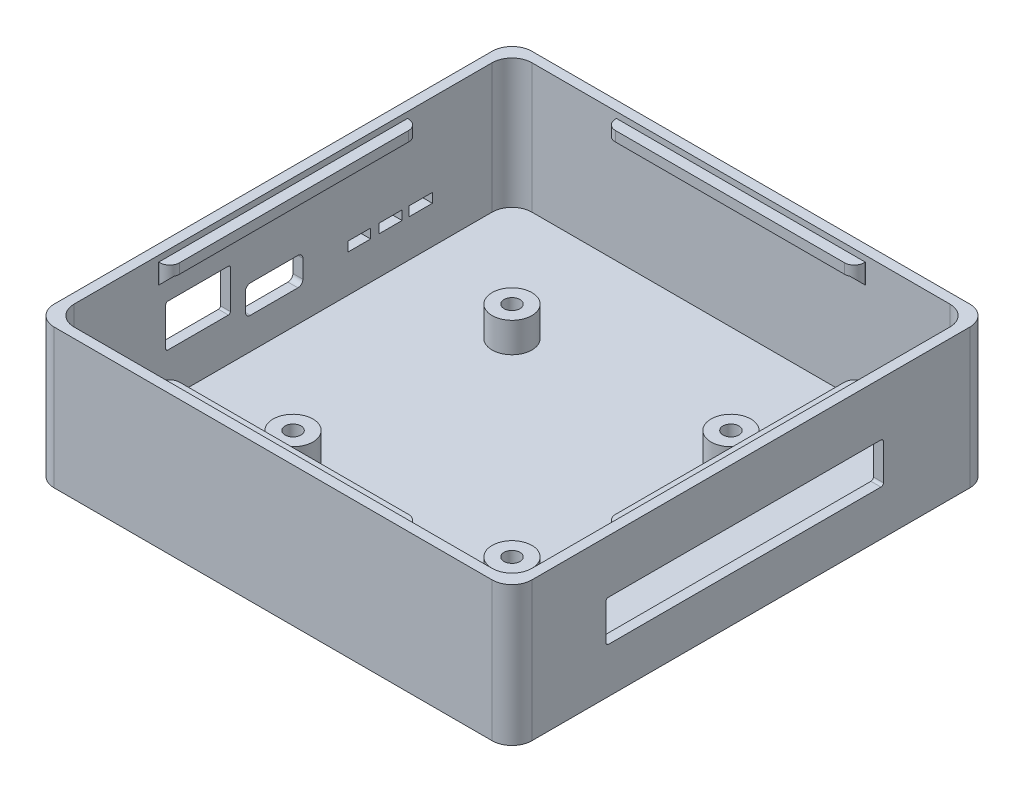
SolidWorks part; units mm, degrees
ref_plane "前视基准面" through (0, 0, 0) normal (0, 0, 1) x (1, 0, 0)
ref_plane "上视基准面" through (0, 0, 0) normal (0, 1, 0) x (1, 0, 0)
ref_plane "右视基准面" through (0, 0, 0) normal (1, 0, 0) x (0, 0, -1)
other "Configuration Table"
sketch "草图1" plane through (0, 0, 0) normal (0, 1, 0) x (1, 0, 0)
  line L1 (0, 0) -> (96, 0)
  line L2 (0, 0) -> (0, -96)
  line L3 (0, -96) -> (96, -96)
  line L4 (96, 0) -> (96, -96)
  dimension "D1" = 96
extrude "凸台-拉伸1" add sketch "草图1" along normal blind 28
sketch "草图3" plane through (0, 28, 0) normal (0, 1, 0) x (1, 0, 0)
  line L0 (96, 0) -> (0, 0) construction
  line L1 (2, -2) -> (94, -2)
  line L2 (2, -2) -> (2, -94)
  line L3 (2, -94) -> (94, -94)
  line L4 (94, -2) -> (94, -94)
  line L5 (0, 0) -> (0, -96) construction
  line L6 (96, -96) -> (96, 0) construction
  dimension "D1" = 92
  dimension "D2" = 2
  dimension "D3" = 2
extrude "切除-拉伸1" cut sketch "草图3" against normal offset from surface (26 mm away) 2 up to face at (48, 0, 48)
fillet "圆角1" radius 4 4 edges at (2, 15, 2) (94, 15, 2) (94, 15, 94) (2, 15, 94)
fillet "圆角2" radius 4 4 edges at (96, 14, 96) (0, 14, 96) (0, 14, 0) (96, 14, 0)
sketch "草图4" plane through (0, 2, 0) normal (0, 1, 0) x (1, 0, 0)
  line L0 (6, -2) -> (90, -2) construction
  line L1 (4, -4) -> (92, -4) construction
  line L2 (4, -4) -> (4, -92) construction
  line L3 (4, -92) -> (92, -92) construction
  line L4 (92, -4) -> (92, -92) construction
  line L5 (2, -90) -> (2, -6) construction
  line L6 (48, -4) -> (48, -102.0052) construction
  line L7 (4, -48) -> (92, -48) construction
  line L8 (26, 4.0084) -> (26, -97.7392) construction
  line L9 (70, 4.0084) -> (70, -100.3714) construction
  line L10 (-6.2321, -26) -> (113.0331, -26) construction
  line L11 (-8.2289, -70) -> (112.307, -70) construction
  circle A0 centre (26, -26) radius 4
  circle A1 centre (70, -26) radius 4
  circle A2 centre (70, -70) radius 4
  circle A3 centre (26, -70) radius 4
  dimension "D8" = 8
  dimension "D9" = 22
  dimension "D1" = 88
  dimension "D2" = 2
  dimension "D3" = 2
  dimension "D4" = 22
  dimension "D5" = 22
  dimension "D6" = 22
  dimension "D7" = 22
extrude "凸台-拉伸2" add sketch "草图4" along normal blind 6
sketch "草图5" plane through (0, 8, 0) normal (0, 1, 0) x (1, 0, 0)
  circle A0 centre (26, -26) radius 1.6
  circle A3 centre (70, -26) radius 1.6
  circle A4 centre (26, -70) radius 1.6
  circle A5 centre (70, -70) radius 1.6
  dimension "D1" = 3.2
extrude "切除-拉伸2" cut sketch "草图5" along direction (0, 1, 0) on the side against the normal up to next (8 mm away)
sketch "草图6" plane through (0, 0, 0) normal (-1, 0, 0) x (0, 0, 1)
  line L0 (72.5871, 9.5862) -> (72.5871, 20.0862) construction
  line L1 (58.5871, 19.0862) -> (71.5871, 19.0862)
  line L2 (58.5871, 19.0862) -> (58.5871, 10.5862)
  line L3 (58.5871, 10.5862) -> (71.5871, 10.5862)
  line L4 (71.5871, 19.0862) -> (71.5871, 10.5862)
  line L5 (17.9947, 11.4358) -> (22.6947, 11.4358)
  line L6 (17.9947, 11.4358) -> (17.9947, 9.5358)
  line L7 (17.9947, 9.5358) -> (22.6947, 9.5358)
  line L8 (22.6947, 11.4358) -> (22.6947, 9.5358)
  line L9 (24.0907, 11.4358) -> (28.6907, 11.4358)
  line L10 (24.0907, 11.4358) -> (24.0907, 9.5862)
  line L11 (24.0907, 9.5862) -> (28.6907, 9.5862)
  line L12 (28.6907, 11.4358) -> (28.6907, 9.5862)
  line L13 (30.4137, 11.4358) -> (34.9137, 11.4358)
  line L14 (30.4137, 11.4358) -> (30.4137, 9.5358)
  line L15 (30.4137, 9.5358) -> (34.9137, 9.5358)
  line L16 (34.9137, 11.4358) -> (34.9137, 9.5358)
  line L17 (57.5871, 20.0862) -> (57.5871, 9.5862) construction
  line L18 (72.5871, 20.0862) -> (57.5871, 20.0862) construction
  line L20 (57.5871, 9.5862) -> (72.5871, 9.5862) construction
  line L21 (22.6947, 9.5358) -> (22.6947, 10.3814) construction
  line L22 (17.9947, 9.5358) -> (17.9947, 10.3814) construction
  line L23 (22.4947, 11.4358) -> (18.1947, 11.4358) construction
  line L24 (18.1947, 9.5358) -> (22.4947, 9.5358) construction
  line L26 (28.6907, 10.3814) -> (28.6907, 9.5358) construction
  line L27 (24.0907, 9.5358) -> (24.0907, 10.3814) construction
  line L28 (28.5907, 11.4358) -> (24.2907, 11.4358) construction
  line L29 (28.5208, 9.5862) -> (24.3399, 9.5862) construction
  line L30 (30.4137, 9.5358) -> (30.4137, 10.3814) construction
  line L31 (34.8137, 11.4358) -> (30.5137, 11.4358) construction
  line L32 (30.5137, 9.5358) -> (34.8137, 9.5358) construction
  line L33 (34.9137, 10.3814) -> (34.9137, 9.5358) construction
  line L34 (45.2273, 11.7569) -> (45.2273, 8.9953) construction
  line L35 (44.0273, 13.9797) -> (55.5713, 13.9797)
  line L36 (44.0273, 13.9797) -> (44.0273, 8.3374)
  line L37 (44.0273, 8.3374) -> (55.5713, 8.3374)
  line L38 (55.5713, 13.9797) -> (55.5713, 8.3374)
  line L39 (54.3713, 8.9953) -> (54.3713, 11.7569) construction
  line L40 (46.2501, 12.7797) -> (53.3485, 12.7797) construction
  line L41 (46.2501, 9.5374) -> (53.3485, 9.5374) construction
  point P27 (22.6947, 9.9586)
  point P38 (28.6907, 9.9586)
  dimension "D1" = 1
  dimension "D2" = 1
  dimension "D3" = 1
  dimension "D4" = 1
  dimension "D5" = 0
  dimension "D6" = 0
  dimension "D7" = 0
  dimension "D8" = 0
  dimension "D9" = 0
  dimension "D10" = 0
  dimension "D11" = 0
  dimension "D12" = 0
  dimension "D13" = 0
  dimension "D14" = 0
  dimension "D15" = 0
  dimension "D16" = 0
  dimension "D17" = 1.2
  dimension "D18" = 1.2
  dimension "D19" = 1.2
  dimension "D20" = 1.2
extrude "切除-拉伸3" cut sketch "草图6" along direction (-1, 0, 0) on the side against the normal up to next (2 mm away)
fillet "圆角3" radius 0.4 4 edges at (1, 10.5862, 71.5871) (1, 10.5862, 58.5871) (1, 19.0862, 58.5871) (1, 19.0862, 71.5871)
sketch "草图7" plane through (96, 0, 0) normal (1, 0, 0) x (0, 0, -1)
  line L0 (-75.1321, 13.6862) -> (-75.1321, 9.5862) construction
  line L1 (-77.1321, 17.2862) -> (-21.364, 17.2862)
  line L2 (-77.1321, 17.2862) -> (-77.1321, 9.0862)
  line L3 (-77.1321, 9.0862) -> (-21.364, 9.0862)
  line L4 (-21.364, 17.2862) -> (-21.364, 9.0862)
  line L5 (-23.364, 9.6862) -> (-23.364, 13.5296) construction
  line L6 (-63.2321, 15.2862) -> (-72.0321, 15.2862) construction
  line L7 (-75.1321, 9.5862) -> (-60.1321, 9.5862) construction
  dimension "D1" = 2
  dimension "D2" = 2
  dimension "D3" = 2
  dimension "D4" = 0.5
extrude "切除-拉伸4" cut sketch "草图7" along direction (1, 0, 0) on the side against the normal up to next (2 mm away)
fillet "圆角4" radius 0.5 4 edges at (95, 9.0862, 77.1321) (95, 9.0862, 21.364) (95, 17.2862, 21.364) (95, 17.2862, 77.1321)
fillet "圆角5" radius 1 4 edges at (1, 8.3374, 55.5713) (1, 8.3374, 44.0273) (1, 13.9797, 44.0273) (1, 13.9797, 55.5713)
sketch "草图8" plane through (0, 0, 94) normal (0, 0, -1) x (-1, 0, 0)
  line L0 (-6, 28) -> (-90, 28) construction
  line L1 (-73, 26.8) -> (-23, 26.8)
  line L2 (-73, 26.8) -> (-73, 24.8)
  line L3 (-73, 24.8) -> (-23, 24.8)
  line L4 (-23, 26.8) -> (-23, 24.8)
  line L5 (-48, 12.074) -> (-48, 43.7522) construction
  line L6 (-90, 28) -> (-90, 2) construction
  line L7 (-6, 2) -> (-6, 28) construction
  point P9 (-53.9957, 12.074)
  dimension "D1" = 1.2
  dimension "D2" = 2
  dimension "D3" = 50
extrude "凸台-拉伸3" add sketch "草图8" along normal blind 2.2
fillet "圆角6" radius 2 2 edges at (23, 25.8, 91.8) (73, 25.8, 91.8)
pattern_circular "阵列(圆周)1" count 4 over 360 about axis through (48, 0, 48) along (0, 1, 0) of "凸台-拉伸3"
fillet "圆角7" radius 2 6 edges at (4.2, 25.8, 23) (4.2, 25.8, 73) (73, 25.8, 4.2) (23, 25.8, 4.2) (91.8, 25.8, 73) (91.8, 25.8, 23)
chamfer "倒角1" distance 2 angle 45 1 edges at (48, 24.8, 2)
chamfer "倒角2" distance 2 angle 45 1 edges at (48, 24.8, 94)
chamfer "倒角3" distance 2 angle 45 1 edges at (94, 24.8, 48)
chamfer "倒角4" distance 2 angle 45 1 edges at (2, 24.8, 48)
